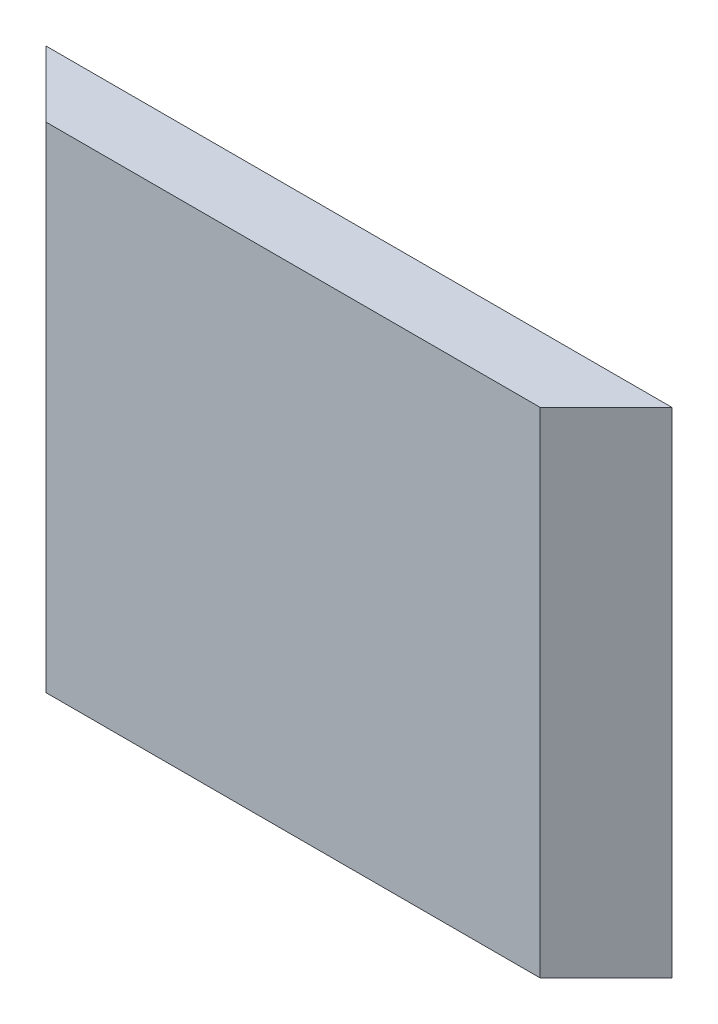
SolidWorks part; units mm, degrees
ref_plane "Front Plane" through (0, 0, 0) normal (0, 0, 1) x (1, 0, 0)
ref_plane "Top Plane" through (0, 0, 0) normal (0, 1, 0) x (1, 0, 0)
ref_plane "Right Plane" through (0, 0, 0) normal (1, 0, 0) x (0, 0, -1)
sketch "Sketch1" plane through (0, 0, 0) normal (0, 0, 1) x (1, 0, 0)
  line L0 (-180.5, -30) -> (-180.5, 0)
  line L1 (-180.5, 0) -> (-140.5, 0)
  line L2 (-140.5, 0) -> (-140.5, -30)
  line L3 (-140.5, -30) -> (-180.5, -30)
extrude "Boss-Extrude1" add sketch "Sketch1" along normal blind 4
chamfer "Chamfer1" distance 5 angle 45 2 edges at (-180.5, -15, 4) (-140.5, -15, 4)
